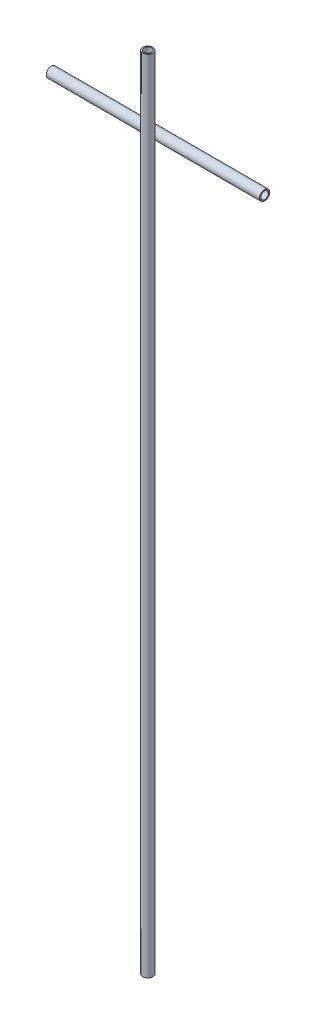
SolidWorks part; units mm, degrees
ref_plane "Plano frontal" through (0, 0, 0) normal (0, 0, 1) x (1, 0, 0)
ref_plane "Plano superior" through (0, 0, 0) normal (0, 1, 0) x (1, 0, 0)
ref_plane "Plano direito" through (0, 0, 0) normal (1, 0, 0) x (0, 0, -1)
sketch "Esboço1" plane through (0, 0, 0) normal (0, 1, 0) x (1, 0, 0)
  circle A0 centre (0, -100) radius 9.525
  circle A1 centre (0, -100) radius 7.275
  dimension "D1" = 2.25
  dimension "D2" = 19.05
extrude "Ressalto-extrusão1" add sketch "Esboço1" along normal blind 500 and the other way blind 1000
sketch "Esboço3" plane through (0, 0, 0) normal (1, 0, 0) x (0, 0, -1)
  line L0 (-90.475, -1000) -> (-90.475, 500) construction
  line L1 (-90, 55) -> (-95, 55) construction
  circle A0 centre (-80.95, 355) radius 9.525
  circle A1 centre (-80.95, 355) radius 7.275
  dimension "D1" = 2.25
  dimension "D2" = 19.05
  dimension "D3" = 300
extrude "Ressalto-extrusão2" add sketch "Esboço3" along normal blind 200 and the other way blind 200 separate body
